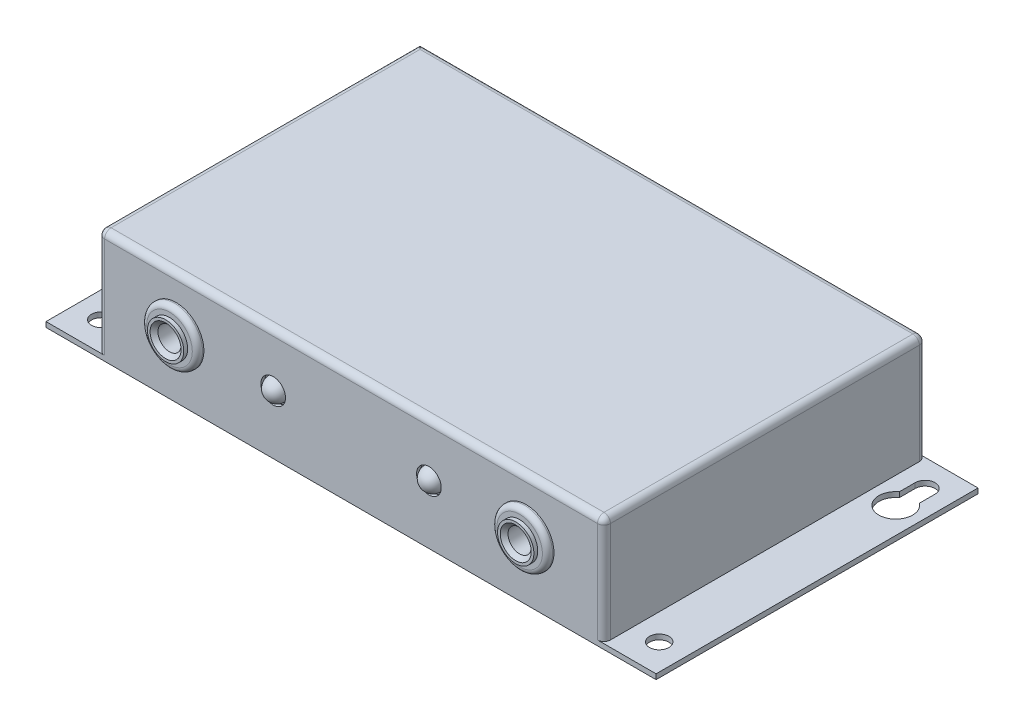
SolidWorks part; units mm, degrees
ref_plane "Front Plane" through (0, 0, 0) normal (0, 0, 1) x (1, 0, 0)
ref_plane "Top Plane" through (0, 0, 0) normal (0, 1, 0) x (1, 0, 0)
ref_plane "Right Plane" through (0, 0, 0) normal (1, 0, 0) x (0, 0, -1)
sketch "Sketch1" plane through (0, 0, 0) normal (0, 1, 0) x (1, 0, 0)
  line L1 (0, 0) -> (99, 0)
  line L2 (0, 0) -> (0, 63)
  line L3 (0, 63) -> (99, 63)
  line L4 (99, 0) -> (99, 63)
  dimension "D1" = 63
  dimension "D2" = 99
extrude "Boss-Extrude1" add sketch "Sketch1" along normal blind 22
sketch "Sketch5" plane through (0, 0, 0) normal (0, -1, 0) x (1, 0, 0)
  line L1 (0, -63) -> (-10.2, -63)
  line L2 (0, -63) -> (0, 0)
  line L3 (0, 0) -> (-10.2, 0)
  line L4 (-10.2, -63) -> (-10.2, 0)
  line L5 (99, -63) -> (109.2, -63)
  line L6 (99, -63) -> (99, 0)
  line L7 (99, 0) -> (109.2, 0)
  line L8 (109.2, -63) -> (109.2, 0)
  dimension "D1" = 63
  dimension "D2" = 10.2
  dimension "D3" = 10.2
  dimension "D4" = 63
extrude "Boss-Extrude3" add sketch "Sketch5" against normal blind 1
sketch "Sketch7" plane through (0, 1, 0) normal (0, 1, 0) x (1, 0, 0)
  line L0 (104.1, 63) -> (104.1, 0) construction
  line L1 (99, 63) -> (109.2, 63) construction
  line L2 (109.2, 0) -> (99, 0) construction
  line L3 (104.1, 59.7) -> (110.2653, 59.7) construction
  line L4 (104.1, 48.7) -> (110.2653, 48.7) construction
  line L5 (102.15, 57.75) -> (102.15, 54.6622)
  line L6 (106.05, 57.75) -> (106.05, 54.6622)
  line L7 (104.1, 3.81) -> (110.2653, 3.81) construction
  line L8 (49.5, 0) -> (49.5, 63) construction
  line L9 (0, 0) -> (99, 0) construction
  line L10 (99, 63) -> (0, 63) construction
  line L11 (-5.1, 3.81) -> (-11.2653, 3.81) construction
  line L12 (-5.1, 48.7) -> (-11.2653, 48.7) construction
  line L13 (-5.1, 59.7) -> (-11.2653, 59.7) construction
  line L14 (-5.1, 63) -> (-5.1, 0) construction
  line L15 (-7.05, 57.75) -> (-7.05, 54.6622)
  line L16 (-3.15, 57.75) -> (-3.15, 54.6622)
  arc A0 (106.05, 57.75) -> (102.15, 57.75) centre (104.1, 57.75) ccw
  arc A1 (102.15, 54.6622) -> (106.05, 54.6622) centre (104.1, 52) ccw
  circle A2 centre (104.1, 5.71) radius 1.9
  circle A3 centre (-5.1, 5.71) radius 1.9
  arc A4 (-3.15, 54.6622) -> (-7.05, 54.6622) centre (-5.1, 52) cw
  arc A5 (-7.05, 57.75) -> (-3.15, 57.75) centre (-5.1, 57.75) cw
  dimension "D1" = 6.6
  dimension "D2" = 3.9
  dimension "D5" = 3.8
  dimension "D3" = 11
  dimension "D4" = 11
  dimension "D6" = 3.81
extrude "Cut-Extrude2" cut sketch "Sketch7" against normal up to surface (1 mm away) up to face at (49.5, 0, -31.5)
sketch "Sketch8" plane through (0, 0, 0) normal (0, 0, 1) x (1, 0, 0)
  line L0 (0, 11.5) -> (99, 11.5) construction
  line L1 (0, 22) -> (0, 1) construction
  line L2 (99, 22) -> (99, 1) construction
  line L3 (49.5, 11.5) -> (49.5, 22) construction
  line L4 (0, 22) -> (99, 22) construction
  circle A0 centre (15.24, 11.5) radius 5.461
  circle A1 centre (83.76, 11.5) radius 5.461
  dimension "D1" = 10.922
  dimension "D2" = 15.24
extrude "Boss-Extrude4" add sketch "Sketch8" along normal blind 1.27
sketch "Sketch9" plane through (0, 0, 1.27) normal (0, 0, 1) x (1, 0, 0)
  circle A0 centre (15.24, 11.5) radius 3.556
  circle A1 centre (83.76, 11.5) radius 3.556
  circle A2 centre (15.24, 11.5) radius 2.032
  circle A3 centre (83.76, 11.5) radius 2.032
  dimension "D1" = 7.112
  dimension "D2" = 7.112
  dimension "D3" = 4.064
  dimension "D4" = 4.064
extrude "Boss-Extrude5" add sketch "Sketch9" along normal blind 0.762
fillet "Fillet1" radius 1 2 edges at (78.299, 11.5, 1.27) (20.701, 11.5, 1.27)
chamfer "Chamfer1" distance 1 angle 45 2 edges at (85.792, 11.5, 2.032) (17.272, 11.5, 2.032)
sketch "Sketch10" plane through (0, 0, 1.27) normal (0, 0, 1) x (1, 0, 0)
  circle A0 centre (15.24, 11.5) radius 2.27
  circle A1 centre (83.76, 11.5) radius 2.27
extrude "Cut-Extrude3" cut sketch "Sketch10" against normal blind 20
sketch "Sketch11" plane through (0, 0, 0) normal (0, 0, 1) x (1, 0, 0)
  line L0 (0, 11.5) -> (99, 11.5) construction
  line L1 (0, 22) -> (0, 1) construction
  line L2 (99, 22) -> (99, 1) construction
  line L3 (49.5, 11.5) -> (49.5, 22) construction
  line L4 (0, 22) -> (99, 22) construction
  circle A0 centre (34.26, 11.5) radius 2.413
  circle A1 centre (64.74, 11.5) radius 2.413
  dimension "D1" = 4.826
  dimension "D2" = 15.24
extrude "Cut-Extrude4" cut sketch "Sketch11" against normal blind 0.762
sketch "Sketch12" plane through (0, 0, -0.762) normal (0, 0, 1) x (1, 0, 0)
  line L0 (34.26, 11.5) -> (34.26, 22) construction
  line L1 (0, 22) -> (99, 22) construction
ref_plane "Plane2" through (34.26, 11.5, -0.762) normal (0, 1, 0) x (1, 0, 0)
sketch "Sketch13" plane through (34.26, 11.5, -0.762) normal (0, 1, 0) x (1, 0, 0)
  line L0 (0, 2.159) -> (0, -2.159)
  line L1 (0, 2.159) -> (0, 5.8082) construction
  arc A0 (0, -2.159) -> (0, 2.159) centre (0, 0) ccw
  dimension "D1" = 4.318
revolve "Revolve1" add sketch "Sketch13" angle 360 about L1
sketch "Sketch15" plane through (34.26, 11.5, -0.762) normal (0, 1, 0) x (1, 0, 0)
  line L0 (0, 0) -> (30.48, 0) construction
  line L1 (30.48, -2.159) -> (30.48, 2.159)
  line L2 (30.48, 2.159) -> (30.48, 3.9005) construction
  arc A0 (30.48, -2.159) -> (30.48, 2.159) centre (30.48, 0) ccw
  dimension "D2" = 4.318
  dimension "D1" = 30.48
revolve "Revolve2" add sketch "Sketch15" angle 360 about L2
fillet "Fillet3" radius 1.27 7 edges at (49.5, 22, -63) (99, 11.5, -63) (99, 22, -31.5) (99, 11.5, 0) (49.5, 22, 0) (0, 11.5, 0) (0, 22, -31.5)
